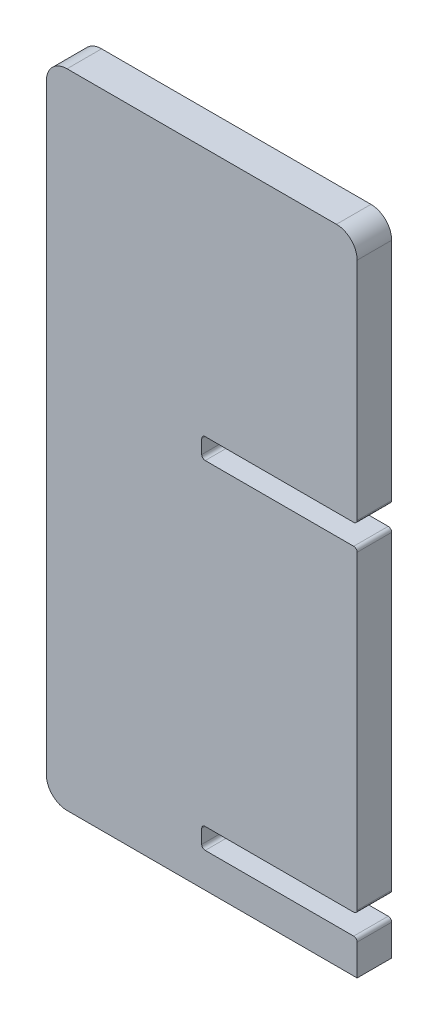
SolidWorks part; units mm, degrees
ref_plane "Alzado" through (0, 0, 0) normal (0, 0, 1) x (1, 0, 0)
ref_plane "Planta" through (0, 0, 0) normal (0, 1, 0) x (1, 0, 0)
ref_plane "Vista lateral" through (0, 0, 0) normal (1, 0, 0) x (0, 0, -1)
sketch "Croquis1" plane through (0, 0, 0) normal (0, 0, 1) x (1, 0, 0)
  line L1 (-22.5, 45) -> (22.5, 45)
  line L2 (-22.5, 45) -> (-22.5, -48)
  line L3 (-22.5, -48) -> (22.5, -48)
  line L4 (22.5, 45) -> (22.5, -48)
  dimension "D1" = 45
  dimension "D2" = 22.5
  dimension "D3" = 93
  dimension "D4" = 45
extrude "Saliente-Extruir1" add sketch "Croquis1" along normal blind 5 contours L2 L3 L4 L1
sketch "Croquis2" plane through (0, 0, 5) normal (0, 0, 1) x (1, 0, 0)
  line L0 (22.5, 45) -> (22.5, -48) construction
  line L1 (22.5, 8.8795) -> (0, 8.8795)
  line L2 (22.5, 8.8795) -> (22.5, 5.8795)
  line L3 (22.5, 5.8795) -> (0, 5.8795)
  line L4 (0, 8.8795) -> (0, 5.8795)
  dimension "D1" = 22.5
  dimension "D2" = 3
  dimension "D3" = 5.8795
extrude "Cortar-Extruir1" cut sketch "Croquis2" against normal up to surface (5 mm away) up to face at (0, -1.5, 0)
sketch "Croquis3" plane through (0, 0, 5) normal (0, 0, 1) x (1, 0, 0)
  line L0 (22.5, 5.8795) -> (22.5, -48) construction
  line L1 (22.5, -40) -> (0, -40)
  line L2 (22.5, -40) -> (22.5, -43)
  line L3 (22.5, -43) -> (0, -43)
  line L4 (0, -40) -> (0, -43)
  line L5 (-22.5, -48) -> (22.5, -48) construction
  dimension "D1" = 3
  dimension "D2" = 5
  dimension "D3" = 22.5
extrude "Cortar-Extruir2" cut sketch "Croquis3" against normal up to surface (5 mm away) up to face at (5.625, 2.9397, 0)
fillet "Redondeo1" radius 3 3 edges at (-22.5, -48, 2.5) (22.5, 45, 2.5) (-22.5, 45, 2.5)
fillet "Redondeo2" radius 0.5 8 edges at (22.5, 5.8795, 2.5) (22.5, 8.8795, 2.5) (0, 8.8795, 2.5) (0, 5.8795, 2.5) (22.5, -43, 2.5) (0, -43, 2.5) (0, -40, 2.5) (22.5, -40, 2.5)
